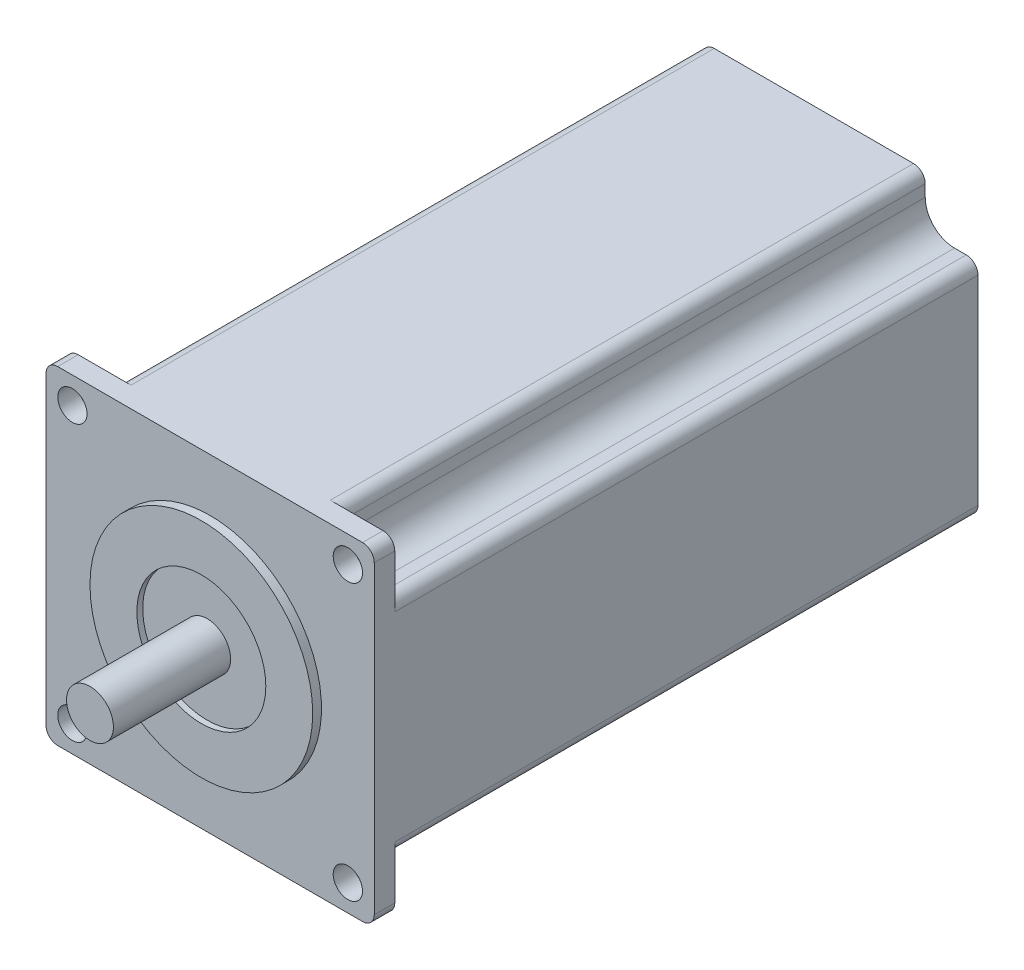
SolidWorks part; units mm, degrees
ref_plane "前视基准面" through (0, 0, 0) normal (0, 0, 1) x (1, 0, 0)
ref_plane "上视基准面" through (0, 0, 0) normal (0, 1, 0) x (1, 0, 0)
ref_plane "右视基准面" through (0, 0, 0) normal (1, 0, 0) x (0, 0, -1)
sketch "草图1" plane through (0, 0, 0) normal (0, 0, 1) x (1, 0, 0)
  line L1 (0, 0) -> (56, 0)
  line L2 (0, 0) -> (0, 56)
  line L3 (0, 56) -> (56, 56)
  line L4 (56, 0) -> (56, 56)
  dimension "D1" = 56
  dimension "D2" = 56
extrude "凸台-拉伸1" add sketch "草图1" along normal blind 103
sketch "草图2" plane through (0, 0, 0) normal (0, 0, -1) x (-1, 0, 0)
  line L0 (-56, 0) -> (-56, 56) construction
  line L1 (0, 0) -> (-56, 0) construction
  line L3 (-56, 0) -> (-47, 0)
  line L4 (-56, 0) -> (-56, 9)
  line L5 (-56, 9) -> (-47, 9)
  line L6 (-47, 0) -> (-47, 9)
  line L7 (-56, 56) -> (-47, 56)
  line L8 (-56, 56) -> (-56, 47)
  line L9 (-56, 47) -> (-47, 47)
  line L10 (-47, 56) -> (-47, 47)
  line L11 (0, 56) -> (-9, 56)
  line L12 (0, 56) -> (0, 47)
  line L13 (0, 47) -> (-9, 47)
  line L14 (-9, 56) -> (-9, 47)
  line L15 (0, 0) -> (-9, 0)
  line L16 (0, 0) -> (0, 9)
  line L17 (0, 9) -> (-9, 9)
  line L18 (-9, 0) -> (-9, 9)
  circle A0 centre (-51.5, 51.5) radius 2.5 construction
  circle A1 centre (-4.5, 51.5) radius 2.5 construction
  circle A2 centre (-4.5, 4.5) radius 2.5 construction
  circle A3 centre (-51.5, 4.5) radius 2.5 construction
  dimension "D1" = 5
  dimension "D2" = 5
  dimension "D3" = 5
  dimension "D4" = 5
  dimension "D5" = 47
  dimension "D6" = 47
  dimension "D7" = 4.5
  dimension "D8" = 4.5
  dimension "D9" = 9
  dimension "D10" = 9
  dimension "D11" = 9
  dimension "D12" = 9
  dimension "D13" = 9
  dimension "D14" = 9
  dimension "D15" = 9
  dimension "D16" = 9
extrude "切除-拉伸1" cut sketch "草图2" against normal blind 99.5
hole_wizard "Ø5.0 (5) 直径孔1" positions "草图4" profile "草图3" hole size "Ø5.0" standard "GB"
sketch "草图4" plane through (0, 0, 103) normal (0, 0, 1) x (1, 0, 0)
  line L0 (0, 0) -> (56, 0) construction
  line L1 (0, 56) -> (0, 0) construction
  point P0 (4.5, 51.5)
  point P2 (51.5, 51.5)
  point P4 (51.5, 4.5)
  point P6 (4.5, 4.5)
  point P17 (0.7526, 26.9282)
  point P22 (6.2811, 38.8877)
  dimension "D1" = 47
  dimension "D2" = 47
  dimension "D3" = 4.5
  dimension "D4" = 4.5
sketch "草图3" plane through (4.5, 51.5, 103) normal (1, 0, 0) x (0, -1, 0)
  line L0 (0, 0) -> (0, 11.5022)
  line L1 (0, 11.5022) -> (2.5, 10)
  line L2 (2.5, 10) -> (2.5, 0)
  line L5 (2.5, 0) -> (0, 0)
  line L10 (0, 11.5022) -> (-2.5, 10) construction
  line L11 (0, -6.35) -> (0, 107.95) construction
  dimension "孔直径" = 5
  dimension "孔深度" = 10
  dimension "导头角度" = 118
fillet "圆角2" radius 5 4 edges at (9, 9, 49.75) (47, 9, 49.75) (9, 47, 49.75) (47, 47, 49.75)
sketch "草图5" plane through (0, 0, 103) normal (0, 0, 1) x (1, 0, 0)
  line L0 (0, 0) -> (56, 0) construction
  line L1 (0, 56) -> (0, 0) construction
  circle A0 centre (28, 28) radius 19
  dimension "D1" = 38
  dimension "D2" = 28
  dimension "D3" = 28
extrude "凸台-拉伸2" add sketch "草图5" along normal blind 1.5
sketch "草图6" plane through (0, 0, 104.5) normal (0, 0, 1) x (1, 0, 0)
  circle A0 centre (28, 28) radius 11
  dimension "D1" = 22
extrude "切除-拉伸2" cut sketch "草图6" against normal blind 1
sketch "草图7" plane through (0, 0, 103.5) normal (0, 0, 1) x (1, 0, 0)
  circle A0 centre (28, 28) radius 4
  dimension "D1" = 8
extrude "凸台-拉伸3" add sketch "草图7" along normal blind 20
fillet "圆角3" radius 2 12 edges at (0, 0, 101.25) (56, 0, 101.25) (56, 56, 101.25) (0, 56, 101.25) (0, 9, 49.75) (9, 0, 49.75) (47, 0, 49.75) (56, 9, 49.75) (56, 47, 49.75) (47, 56, 49.75) (0, 47, 49.75) (9, 56, 49.75)
sketch "草图8" plane through (0, 0, 0) normal (0, 0, -1) x (-1, 0, 0)
  line L0 (-11, 0) -> (-45, 0) construction
  line L2 (-56, 11) -> (-56, 45) construction
  circle A0 centre (-28, 28) radius 26
  dimension "D1" = 52
  dimension "D2" = 28
  dimension "D3" = 28
extrude "凸台-拉伸4" add sketch "草图8" along normal blind 1.5
chamfer "倒角1" distance 1.5 angle 75 1 edges at (2, 28, -1.5) first distance on face at (2, 28, -1.5)
